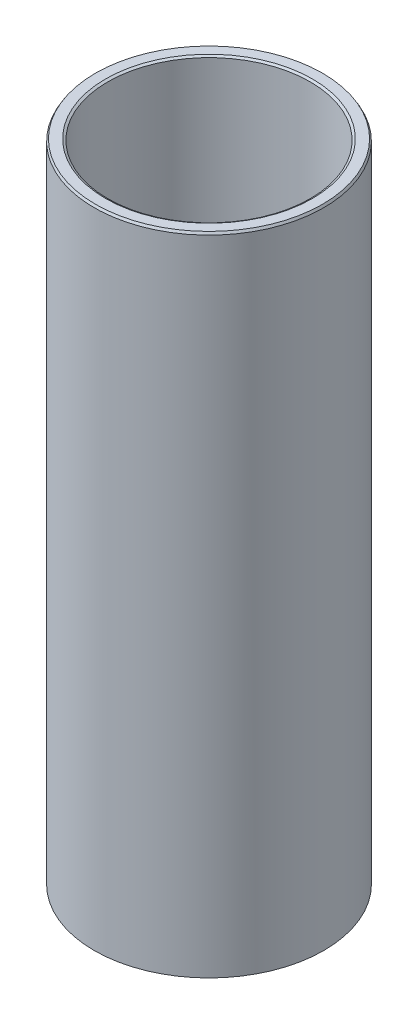
SolidWorks part; units mm, degrees
ref_plane "Front Plane" through (0, 0, 0) normal (0, 0, 1) x (1, 0, 0)
ref_plane "Top Plane" through (0, 0, 0) normal (0, 1, 0) x (1, 0, 0)
ref_plane "Right Plane" through (0, 0, 0) normal (1, 0, 0) x (0, 0, -1)
sketch "Sketch1" plane through (0, 0, 0) normal (0, 1, 0) x (1, 0, 0)
  circle A0 centre (0, 0) radius 37.5
  dimension "SLEEVE_OD" = 75
extrude "Boss-Extrude1" add sketch "Sketch1" along normal blind 211.1823
sketch "Sketch2" plane through (0, 0, 0) normal (0, 1, 0) x (1, 0, 0)
  circle A0 centre (0, 0) radius 33.0434
  dimension "BORE_D" = 66.0868
extrude "Cut-Extrude1" cut sketch "Sketch2" along normal through all
chamfer "Chamfer1" distance 0.7456 angle 30 4 edges at (0, 211.1823, 33.0434) (0, 0, 33.0434) (0, 0, 37.5) (0, 211.1823, 37.5) first distance on face at (0, 211.1823, 33.0434) first distance on face at (0, 0, 33.0434) first distance on face at (0, 211.1823, 37.5)
